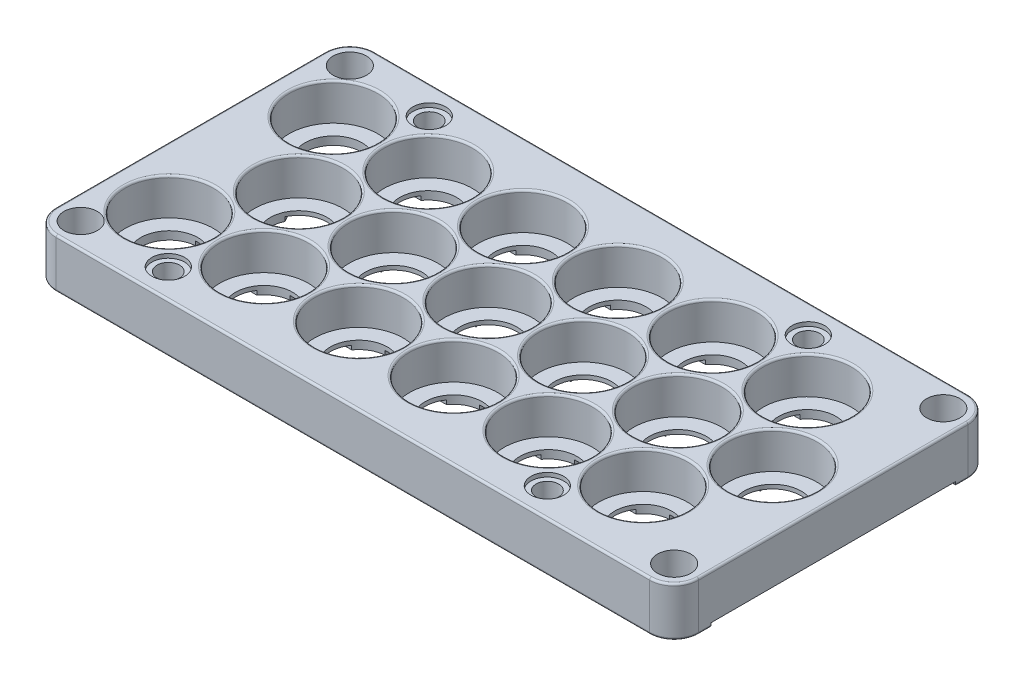
SolidWorks part; units mm, degrees
ref_plane "Front Plane" through (0, 0, 0) normal (0, 0, 1) x (1, 0, 0)
ref_plane "Top Plane" through (0, 0, 0) normal (0, 1, 0) x (1, 0, 0)
ref_plane "Right Plane" through (0, 0, 0) normal (1, 0, 0) x (0, 0, -1)
sketch "Sketch1" plane through (0, 0, 0) normal (0, 1, 0) x (1, 0, 0)
  line L0 (0, 0) -> (11.575, -20.0485) construction
  line L1 (11.575, -20.0485) -> (0, -40.097) construction
  line L2 (0, 0) -> (11.575, 0) construction
  line L3 (11.575, 0) -> (11.575, -20.0485) construction
  line L4 (11.575, -20.0485) -> (11.575, -40.097) construction
  line L5 (11.575, -40.097) -> (0, -40.097) construction
  line L6 (0, 0) -> (23.15, 0) construction
  line L7 (0, 0) -> (23.15, 0) construction
  line L8 (-14.825, -58.922) -> (142.15, -58.922)
  line L9 (-14.825, -58.922) -> (-14.825, 18.825)
  line L10 (-14.825, 18.825) -> (142.15, 18.825)
  line L11 (142.15, -58.922) -> (142.15, 18.825)
  circle A0 centre (0, 0) radius 10.825
  circle A1 centre (11.575, -20.0485) radius 10.825
  circle A2 centre (0, -40.097) radius 10.825
  circle A3 centre (23.15, 0) radius 10.825
  circle A4 centre (34.725, -20.0485) radius 10.825
  circle A5 centre (23.15, -40.097) radius 10.825
  circle A6 centre (46.3, 0) radius 10.825
  circle A7 centre (57.875, -20.0485) radius 10.825
  circle A8 centre (46.3, -40.097) radius 10.825
  circle A9 centre (69.45, 0) radius 10.825
  circle A10 centre (81.025, -20.0485) radius 10.825
  circle A11 centre (69.45, -40.097) radius 10.825
  circle A12 centre (92.6, 0) radius 10.825
  circle A13 centre (104.175, -20.0485) radius 10.825
  circle A14 centre (92.6, -40.097) radius 10.825
  circle A15 centre (115.75, 0) radius 10.825
  circle A16 centre (127.325, -20.0485) radius 10.825
  circle A17 centre (115.75, -40.097) radius 10.825
  circle A18 centre (0, 0) radius 7
  circle A19 centre (11.575, -20.0485) radius 7
  circle A20 centre (0, -40.097) radius 7
  circle A21 centre (23.15, 0) radius 7
  circle A22 centre (34.725, -20.0485) radius 7
  circle A23 centre (23.15, -40.097) radius 7
  circle A24 centre (46.3, 0) radius 7
  circle A25 centre (57.875, -20.0485) radius 7
  circle A26 centre (46.3, -40.097) radius 7
  circle A27 centre (69.45, 0) radius 7
  circle A28 centre (81.025, -20.0485) radius 7
  circle A29 centre (69.45, -40.097) radius 7
  circle A30 centre (92.6, 0) radius 7
  circle A31 centre (104.175, -20.0485) radius 7
  circle A32 centre (92.6, -40.097) radius 7
  circle A33 centre (115.75, 0) radius 7
  circle A34 centre (127.325, -20.0485) radius 7
  circle A35 centre (115.75, -40.097) radius 7
  dimension "D3" = 21.65
  dimension "D11" = 14
  dimension "D1" = 60
  dimension "D2" = 60
  dimension "D4" = 1.5
  dimension "D6" = 23.15
  dimension "D7" = 4
  dimension "D8" = 4
  dimension "D9" = 8
  dimension "D10" = 8
  dimension "D13" = 23.15
  dimension "D12" = 6
extrude "Boss-Extrude2" add sketch "Sketch1" along normal blind 11 contours L8 L11 L10 L9 A17 A16 A15 A14 A13 A12 A11 A10 A9 A8 A7 A6 A5 A4 A3 A2 A1 A0 region at (-13.0733, 0, 20.0485)
extrude "Boss-Extrude3" add sketch "Sketch1<3>" along normal blind 2 contours A0 A18 | A3 A21 | A6 A24 | A9 A27 | A12 A30 | A15 A33 | A1 A19 | A4 A22 | A7 A25 | A10 A28 | A13 A31 | A16 A34 | A17 A35 | A14 A32 | A11 A29 | A8 A26 | A5 A23 | A2 A20 region at (-10.5188, 0, 0) region at (1.0562, 0, 20.0485) region at (-10.5188, 0, 40.097) region at (12.6312, 0, 0) region at (24.2062, 0, 20.0485) region at (12.6312, 0, 40.097) region at (35.7812, 0, 0) region at (47.3562, 0, 20.0485) region at (35.7812, 0, 40.097) region at (58.9312, 0, 0) region at (70.5062, 0, 20.0485) region at (58.9312, 0, 40.097) region at (82.0812, 0, 0) region at (93.6562, 0, 20.0485) region at (82.0812, 0, 40.097) region at (105.2312, 0, 0) region at (116.8062, 0, 20.0485) region at (105.2312, 0, 40.097)
sketch "Sketch1<3>" plane through (0, 0, 0) normal (0, 1, 0) x (1, 0, 0) same geometry as "Sketch1"
sketch "Sketch2" plane through (0, 0, 0) normal (0, -1, 0) x (1, 0, 0)
  line L0 (0, 40.097) -> (11.575, 20.0485) construction
  line L1 (3.4641, 42.097) -> (15.0391, 22.0485)
  line L2 (-3.4641, 38.097) -> (8.1109, 18.0485)
  line L3 (11.575, 20.0485) -> (0, 0) construction
  line L4 (15.0391, 18.0485) -> (3.4641, -2)
  line L5 (8.1109, 22.0485) -> (-3.4641, 2)
  line L6 (19.6859, 38.097) -> (31.2609, 18.0485)
  line L7 (26.6141, 42.097) -> (38.1891, 22.0485)
  line L8 (31.2609, 22.0485) -> (19.6859, 2)
  line L9 (38.1891, 18.0485) -> (26.6141, -2)
  line L10 (23.15, 40.097) -> (34.725, 20.0485) construction
  line L11 (34.725, 20.0485) -> (23.15, 0) construction
  line L12 (42.8359, 38.097) -> (54.4109, 18.0485)
  line L13 (49.7641, 42.097) -> (61.3391, 22.0485)
  line L14 (54.4109, 22.0485) -> (42.8359, 2)
  line L15 (61.3391, 18.0485) -> (49.7641, -2)
  line L16 (46.3, 40.097) -> (57.875, 20.0485) construction
  line L17 (57.875, 20.0485) -> (46.3, 0) construction
  line L18 (65.9859, 38.097) -> (77.5609, 18.0485)
  line L19 (72.9141, 42.097) -> (84.4891, 22.0485)
  line L20 (77.5609, 22.0485) -> (65.9859, 2)
  line L21 (84.4891, 18.0485) -> (72.9141, -2)
  line L22 (69.45, 40.097) -> (81.025, 20.0485) construction
  line L23 (81.025, 20.0485) -> (69.45, 0) construction
  line L24 (89.1359, 38.097) -> (100.7109, 18.0485)
  line L25 (96.0641, 42.097) -> (107.6391, 22.0485)
  line L26 (100.7109, 22.0485) -> (89.1359, 2)
  line L27 (107.6391, 18.0485) -> (96.0641, -2)
  line L28 (92.6, 40.097) -> (104.175, 20.0485) construction
  line L29 (104.175, 20.0485) -> (92.6, 0) construction
  line L30 (112.2859, 38.097) -> (123.8609, 18.0485)
  line L31 (119.2141, 42.097) -> (130.7891, 22.0485)
  line L32 (123.8609, 22.0485) -> (112.2859, 2)
  line L33 (130.7891, 18.0485) -> (119.2141, -2)
  line L34 (115.75, 40.097) -> (127.325, 20.0485) construction
  line L35 (127.325, 20.0485) -> (115.75, 0) construction
  line L36 (-3.4641, 38.097) -> (19.6859, 38.097) construction
  line L37 (0, 40.097) -> (115.75, 40.097) construction
  line L38 (0, 44.097) -> (115.75, 44.097)
  line L39 (0, 36.097) -> (115.75, 36.097)
  line L40 (11.575, 20.0485) -> (127.325, 20.0485) construction
  line L41 (11.575, 24.0485) -> (127.325, 24.0485)
  line L42 (11.575, 16.0485) -> (127.325, 16.0485)
  line L43 (0, 0) -> (115.75, 0) construction
  line L44 (0, 4) -> (115.75, 4)
  line L45 (0, -4) -> (115.75, -4)
  arc A0 (3.4641, 42.097) -> (-3.4641, 38.097) centre (0, 40.097) ccw
  arc A1 (8.1109, 18.0485) -> (15.0391, 22.0485) centre (11.575, 20.0485) ccw
  arc A2 (15.0391, 18.0485) -> (8.1109, 22.0485) centre (11.575, 20.0485) ccw
  arc A3 (-3.4641, 2) -> (3.4641, -2) centre (0, 0) ccw
  arc A4 (26.6141, 42.097) -> (19.6859, 38.097) centre (23.15, 40.097) ccw
  arc A5 (31.2609, 18.0485) -> (38.1891, 22.0485) centre (34.725, 20.0485) ccw
  arc A6 (38.1891, 18.0485) -> (31.2609, 22.0485) centre (34.725, 20.0485) ccw
  arc A7 (19.6859, 2) -> (26.6141, -2) centre (23.15, 0) ccw
  arc A8 (49.7641, 42.097) -> (42.8359, 38.097) centre (46.3, 40.097) ccw
  arc A9 (54.4109, 18.0485) -> (61.3391, 22.0485) centre (57.875, 20.0485) ccw
  arc A10 (61.3391, 18.0485) -> (54.4109, 22.0485) centre (57.875, 20.0485) ccw
  arc A11 (42.8359, 2) -> (49.7641, -2) centre (46.3, 0) ccw
  arc A12 (72.9141, 42.097) -> (65.9859, 38.097) centre (69.45, 40.097) ccw
  arc A13 (77.5609, 18.0485) -> (84.4891, 22.0485) centre (81.025, 20.0485) ccw
  arc A14 (84.4891, 18.0485) -> (77.5609, 22.0485) centre (81.025, 20.0485) ccw
  arc A15 (65.9859, 2) -> (72.9141, -2) centre (69.45, 0) ccw
  arc A16 (96.0641, 42.097) -> (89.1359, 38.097) centre (92.6, 40.097) ccw
  arc A17 (100.7109, 18.0485) -> (107.6391, 22.0485) centre (104.175, 20.0485) ccw
  arc A18 (107.6391, 18.0485) -> (100.7109, 22.0485) centre (104.175, 20.0485) ccw
  arc A19 (89.1359, 2) -> (96.0641, -2) centre (92.6, 0) ccw
  arc A20 (119.2141, 42.097) -> (112.2859, 38.097) centre (115.75, 40.097) ccw
  arc A21 (123.8609, 18.0485) -> (130.7891, 22.0485) centre (127.325, 20.0485) ccw
  arc A22 (130.7891, 18.0485) -> (123.8609, 22.0485) centre (127.325, 20.0485) ccw
  arc A23 (112.2859, 2) -> (119.2141, -2) centre (115.75, 0) ccw
  arc A24 (0, 44.097) -> (0, 36.097) centre (0, 40.097) ccw
  arc A25 (115.75, 36.097) -> (115.75, 44.097) centre (115.75, 40.097) ccw
  arc A26 (11.575, 24.0485) -> (11.575, 16.0485) centre (11.575, 20.0485) ccw
  arc A27 (127.325, 16.0485) -> (127.325, 24.0485) centre (127.325, 20.0485) ccw
  arc A28 (0, 4) -> (0, -4) centre (0, 0) ccw
  arc A29 (115.75, -4) -> (115.75, 4) centre (115.75, 0) ccw
  point P3 (5.7875, 30.0727)
  point P8 (5.7875, 10.0242)
  point P18 (28.9375, 30.0727)
  point P25 (28.9375, 10.0242)
  point P34 (52.0875, 30.0727)
  point P39 (52.0875, 10.0242)
  point P48 (75.2375, 30.0727)
  point P53 (75.2375, 10.0242)
  point P62 (98.3875, 30.0727)
  point P67 (98.3875, 10.0242)
  point P76 (121.5375, 30.0727)
  point P81 (121.5375, 10.0242)
  point P91 (57.875, 40.097)
  point P96 (69.45, 20.0485)
  point P103 (57.875, 0)
  circle M62 centre (0, 0) radius 7
  circle M63 centre (23.15, 0) radius 7
  circle M64 centre (46.3, 0) radius 7
  circle M65 centre (69.45, 0) radius 7
  circle M66 centre (92.6, 0) radius 7
  circle M67 centre (115.75, 0) radius 7
  circle M68 centre (11.575, 20.0485) radius 7
  circle M69 centre (34.725, 20.0485) radius 7
  circle M70 centre (57.875, 20.0485) radius 7
  circle M71 centre (81.025, 20.0485) radius 7
  circle M72 centre (104.175, 20.0485) radius 7
  circle M73 centre (127.325, 20.0485) radius 7
  circle M74 centre (115.75, 40.097) radius 7
  circle M75 centre (92.6, 40.097) radius 7
  circle M76 centre (69.45, 40.097) radius 7
  circle M77 centre (46.3, 40.097) radius 7
  circle M78 centre (23.15, 40.097) radius 7
  circle M79 centre (0, 40.097) radius 7
  dimension "D1" = 8
  dimension "D3" = 23.15
  dimension "D4" = 8
  dimension "D5" = 8
  dimension "D6" = 8
extrude "Cut-Extrude1" cut sketch "Sketch2" against normal blind 1 contours L1 L39 L38 M78 M79 | L7 L39 L38 M77 M78 | L39 L2 L1 M79 M68 | L42 L8 L6 L41 M68 M69 | L6 L41 L7 L39 M69 M78 | L12 L41 L13 L39 M70 M77 | L13 L39 L38 M76 M77 | L18 L41 L19 L39 M71 M76 | L19 L39 L38 M75 M76 | L24 L41 L25 L39 M72 M75 | L25 L39 L38 M74 M75 | L30 L41 L31 M73 M74 | L42 L32 L30 L41 M72 M73 | L42 L26 L24 L41 M71 M72 | L42 L20 L18 L41 M70 M71 | L42 L14 L12 L41 M69 M70 | L45 L44 L4 M62 M63 | L44 L4 L5 M62 M68 | L45 L44 L9 M63 M64 | L45 L44 L15 M64 M65 | L45 L44 L21 M65 M66 | L45 L44 L27 M66 M67 | L44 L27 L42 L26 M66 M72 | L42 L32 L33 M67 M73 | L44 L21 L42 L20 M65 M71 | L44 L15 L42 L14 M64 M70 | L39 L13 M77 | L39 L25 M75 | L39 L19 M76 | L41 L6 M69 | L44 L4 M62 | L44 L15 M64 | L44 L21 M65 | L44 L27 M66 | L41 L30 M73 | L32 L42 M73 | L41 L24 M72 | L26 L42 M72 | L41 L18 M71 | L20 L42 M71 | L41 L12 M70 | L14 L42 M70 | L44 L9 L42 L8 M63 M69 | L8 L42 M69 | L39 L7 M78 | L39 L1 M79 | L44 A29 L45 A28 region at (11.6138, 0, 40.1242) region at (6.3461, 0, 36.4331) region at (5.7834, 0, 30.0255) region at (23.0718, 0, 20.0485) region at (28.9375, 0, 30.0727) region at (34.7638, 0, 40.1242) region at (28.3789, 0, 23.7124) region at (5.7834, 0, 10.0715) region at (29.4961, 0, 36.4331) region at (57.9138, 0, 40.1242) region at (28.3789, 0, 16.3846) region at (28.9375, 0, 10.0242) region at (6.3461, 0, 3.6639) region at (11.6138, 0, -0.0272) region at (52.0875, 0, 30.0727) region at (46.2218, 0, 20.0485) region at (52.6461, 0, 36.4331) region at (81.0638, 0, 40.1242) region at (51.5289, 0, 23.7124) region at (34.7638, 0, -0.0272) region at (75.2375, 0, 30.0727) region at (75.7961, 0, 36.4331) region at (104.2138, 0, 40.1242) region at (74.6789, 0, 23.7124) region at (69.3718, 0, 20.0485) region at (51.5289, 0, 16.3846) region at (52.0875, 0, 10.0242) region at (57.9138, 0, -0.0272) region at (98.3875, 0, 30.0727) region at (98.9461, 0, 36.4331) region at (97.8289, 0, 23.7124) region at (92.5218, 0, 20.0485) region at (74.6789, 0, 16.3846) region at (52.6461, 0, 3.6639) region at (81.0638, 0, -0.0272) region at (121.5416, 0, 30.12) region at (75.2375, 0, 10.0242) region at (120.9789, 0, 23.7124) region at (115.6718, 0, 20.0485) region at (97.8289, 0, 16.3846) region at (75.7961, 0, 3.6639) region at (104.2138, 0, -0.0272) region at (98.3875, 0, 10.0242) region at (121.5416, 0, 9.977) region at (120.9789, 0, 16.3846) region at (98.9461, 0, 3.6639)
sketch "Sketch9" plane through (0, 11, 0) normal (0, 1, 0) x (1, 0, 0)
  line L0 (11.575, -58.922) -> (11.575, 18.825)
  line L1 (-14.825, 18.825) -> (142.15, 18.825) construction
  line L2 (104.175, 18.825) -> (104.175, -58.922)
  line L3 (-14.825, -58.922) -> (142.15, -58.922) construction
  circle A0 centre (11.575, 11.825) radius 2.75
  circle A1 centre (11.575, -51.922) radius 2.75
  circle A2 centre (104.175, -51.922) radius 2.75
  circle A3 centre (104.175, 11.825) radius 2.75
  point P0 (11.575, 11.825)
  point P7 (11.575, -20.0485)
  point P15 (104.175, -20.0485)
  point P20 (104.175, 11.825)
  point P21 (104.175, -51.922)
  point P22 (11.575, -51.922)
  dimension "D5" = 5.5
  dimension "D1" = 7
  dimension "D4" = 7
extrude "Cut-Extrude3" cut sketch "Sketch9" against normal up to next contours A2 | A1 | A0 | A3
sketch "Sketch12" plane through (0, 11, 0) normal (0, 1, 0) x (1, 0, 0)
  circle A0 centre (11.575, 11.825) radius 4
  circle A1 centre (104.175, 11.825) radius 4
  circle A2 centre (11.575, -51.922) radius 4
  circle A3 centre (104.175, -51.922) radius 4
  dimension "D1" = 8
extrude "Cut-Extrude4" cut sketch "Sketch12" against normal blind 1
sketch "Sketch11" plane through (0, 0, 0) normal (0, -1, 0) x (1, 0, 0)
  line L0 (142.15, 58.922) -> (142.15, -18.825) construction
  line L1 (-14.825, 58.922) -> (142.15, 58.922)
  line L2 (-14.825, 58.922) -> (-14.825, 49.922)
  line L3 (-14.825, 49.922) -> (142.15, 49.922)
  line L4 (142.15, 58.922) -> (142.15, 49.922)
  line L5 (11.575, 20.0485) -> (104.175, 20.0485) construction
  line L6 (142.15, -18.825) -> (142.15, -9.825)
  line L7 (-14.825, -9.825) -> (142.15, -9.825)
  line L8 (-14.825, -18.825) -> (-14.825, -9.825)
  line L9 (-14.825, -18.825) -> (142.15, -18.825)
  circle A0 centre (11.575, 51.922) radius 6
  circle A1 centre (104.175, 51.922) radius 6
  circle A2 centre (11.575, 51.922) radius 6.875
  circle A3 centre (104.175, 51.922) radius 6.875
  circle A4 centre (104.175, -11.825) radius 6.875
  circle A5 centre (11.575, -11.825) radius 6.875
  circle A6 centre (104.175, -11.825) radius 6
  circle A7 centre (11.575, -11.825) radius 6
  line M9 (142.15, 58.922) -> (-14.825, 58.922)
  line M10 (-14.825, 58.922) -> (-14.825, -18.825)
  line M11 (-14.825, -18.825) -> (142.15, -18.825)
  line M12 (142.15, -18.825) -> (142.15, 58.922)
  dimension "D2" = 12
  dimension "D3" = 13.75
  dimension "D1" = 9
extrude "Boss-Extrude5" add sketch "Sketch11" along normal blind 1 contours A3 L3 A2 M12 M9 M10 | L7 A5 A4 M10 M11 M12 | L3 A2 A0 | L3 A2 A0 | L3 A3 A1 | L3 A3 A1 | L7 A6 A4 | L7 A6 A4 | L7 A7 A5 | L7 A7 A5 region at (64.632, 0, 54.5272) region at (10.5881, 0, 58.5604) region at (5.4577, 0, 49.7817) region at (64.632, 0, -14.4302) region at (104.175, 0, 45.1873) region at (110.2923, 0, 50.0856) region at (11.575, 0, -5.0903) region at (5.4577, 0, -9.9887) region at (110.8134, 0, -10.8381) region at (110.2923, 0, -9.6847)
fillet "Fillet2" radius 6 4 edges at (142.15, 5, 58.922) (142.15, 5, -18.825) (-14.825, 5, -18.825) (-14.825, 5, 58.922)
fillet "Fillet4" radius 0.5 26 edges at (-13.0676, 11, 57.1646) (-14.825, 11, 20.0485) (-13.0676, 11, -17.0676) (63.6625, 11, -18.825) (140.3926, 11, -17.0676) (142.15, 11, 20.0485) (140.3926, 11, 57.1646) (63.6625, 11, 58.922) (0, 11, 10.825) (11.575, 11, 30.8735) (0, 11, 50.922) (23.15, 11, 10.825) (34.725, 11, 30.8735) (23.15, 11, 50.922) (46.3, 11, 10.825) (57.875, 11, 30.8735) (46.3, 11, 50.922) (69.45, 11, 10.825) (81.025, 11, 30.8735) (69.45, 11, 50.922) (92.6, 11, 10.825) (104.175, 11, 30.8735) (92.6, 11, 50.922) (115.75, 11, 10.825) (127.325, 11, 30.8735) (115.75, 11, 50.922)
fillet "Fillet5" radius 0.5 24 edges at (104.175, -1, -17.825) (11.575, -1, -17.825) (-13.0676, -1, -17.0676) (-14.825, -1, -11.325) (-4.9138, -1, -9.825) (11.575, -1, -4.95) (57.875, -1, -9.825) (104.175, -1, -4.95) (126.4513, -1, -9.825) (142.15, -1, -11.325) (140.3926, -1, -17.0676) (63.6625, -1, -18.825) (11.575, -1, 45.922) (104.175, -1, 45.922) (126.4513, -1, 49.922) (104.175, -1, 45.047) (57.875, -1, 49.922) (11.575, -1, 45.047) (-4.9138, -1, 49.922) (-14.825, -1, 51.422) (-13.0676, -1, 57.1646) (63.6625, -1, 58.922) (140.3926, -1, 57.1646) (142.15, -1, 51.422)
sketch "Sketch15" plane through (0, -1, 0) normal (0, -1, 0) x (1, 0, 0)
  line L0 (-8.825, 58.922) -> (136.15, 58.922) construction
  line L1 (-14.825, 49.922) -> (-14.825, 52.922) construction
  line L2 (11.575, 20.0485) -> (104.175, 20.0485) construction
  line L3 (-12.7141, 56.8111) -> (140.0391, 56.8111) construction
  line L4 (63.6625, 56.8111) -> (63.6625, -17.1669) construction
  circle A0 centre (-8.825, 52.922) radius 4.0767
  circle A1 centre (-8.825, -12.825) radius 4.0767
  arc A2 (-8.825, 58.422) -> (-14.325, 52.922) centre (-8.825, 52.922) ccw construction
  arc A3 (141.65, 52.922) -> (136.15, 58.422) centre (136.15, 52.922) ccw construction
  circle A4 centre (136.15, -12.825) radius 4.0767
  circle A5 centre (136.15, 52.922) radius 4.0767
  dimension "D1" = 8.1534
  dimension "D3" = 6
extrude "Cut-Extrude5" cut sketch "Sketch15" against normal blind 20 contours A0 | A1 | A4 | A5
equation "\"hole_diameter\"= 21.65"
equation "\"D3@Sketch1\"=\"hole_diameter\""
equation "\"cell_spacing\"= 1.5"
equation "\"D4@Sketch1\"=\"cell_spacing\""
equation "\"D6@Sketch1\"=\"hole_diameter\"+\"cell_spacing\""
equation "\"len_spacing\"= 4"
equation "\"D7@Sketch1\"=\"len_spacing\""
equation "\"D8@Sketch1\"=\"len_spacing\""
equation "\"wid_spacing\"= 8"
equation "\"D9@Sketch1\"=\"wid_spacing\""
equation "\"D10@Sketch1\"=\"wid_spacing\""
equation "\"nipple\"= 14"
equation "\"D11@Sketch1\"=\"nipple\""
equation "\"D13@Sketch1\"=\"hole_diameter\"+\"cell_spacing\""
equation "\"channel\"= 8"
equation "\"D1@Sketch2\"=\"channel\""
equation "\"D3@Sketch2\"=\"hole_diameter\"+\"cell_spacing\""
equation "\"D4@Sketch2\"=\"channel\""
equation "\"D5@Sketch2\"=\"channel\""
equation "\"D6@Sketch2\"=\"channel\""
equation "\"lip\"= 9"
equation "\"lip_height\"= 1"
equation "\"outer_fillet\"=6"
equation "\"D1@Fillet2\"=\"outer_fillet\""
equation "\"heat_insert\"=5.5"
equation "\"D5@Sketch9\"=\"heat_insert\""
equation "\"insert_placement\"= 7"
equation "\"D4@Sketch9\"=\"insert_placement\""
equation "\"D1@Sketch9\"=\"insert_placement\""
equation "\"heat_insert_lip\"=12"
equation "\"D1@Sketch11\"=\"lip\""
equation "\"D2@Sketch11\"=\"heat_insert_lip\""
equation "\"D3@Sketch11\"= \"heat_insert_lip\" + 1.75"
equation "\"heat_insert_diameter\"=8.1534"
equation "\"D1@Sketch15\"=\"heat_insert_diameter\""
equation "\"heat_insert_space\"=6"
equation "\"D2@Sketch15\"=\"heat_insert_space\""
equation "\"D3@Sketch15\"=\"heat_insert_space\""
